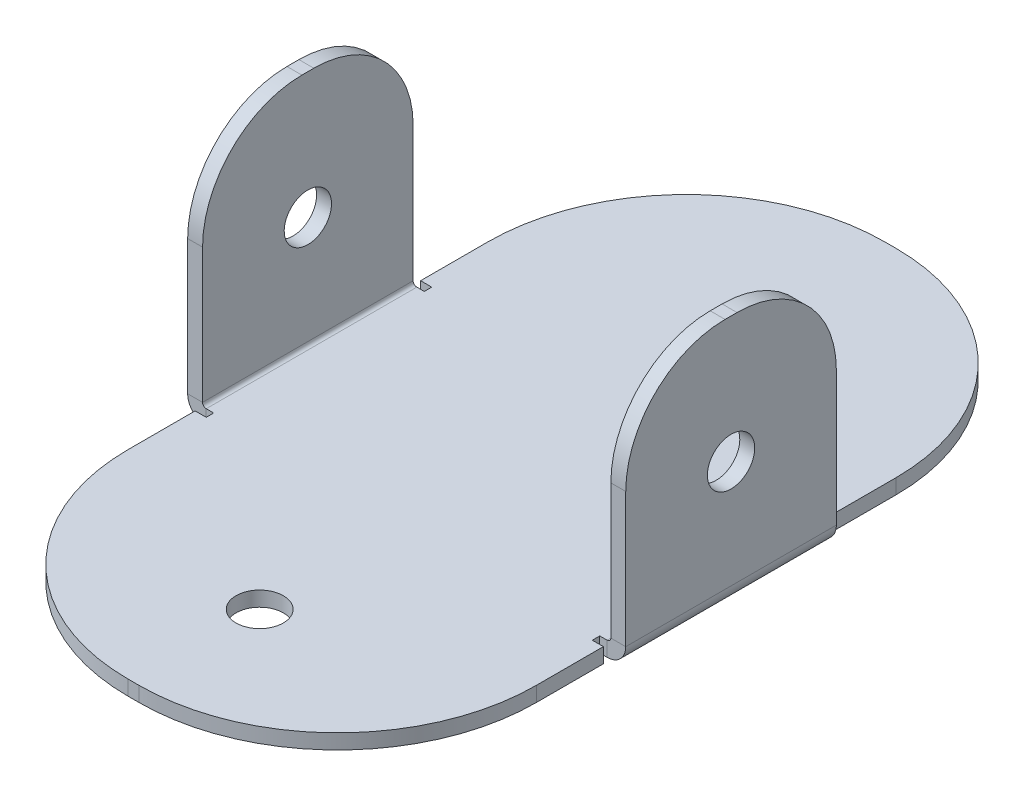
SolidWorks part; units mm, degrees
note: The reader was unsure of these and kept them because the rebuilt part matched: flange length of "Edge-Flange2", "Edge-Flange3".
ref_plane "Front Plane" through (0, 0, 0) normal (0, 0, 1) x (1, 0, 0)
ref_plane "Top Plane" through (0, 0, 0) normal (0, 1, 0) x (1, 0, 0)
ref_plane "Right Plane" through (0, 0, 0) normal (1, 0, 0) x (0, 0, -1)
sketch "Sketch1" plane through (0, 0, 0) normal (0, 1, 0) x (1, 0, 0)
  line L0 (0, -76.2) -> (0, -50.8) construction
  line L1 (-1.1, 76.2) -> (1.1, 76.2)
  line L2 (-41.1, 36.2) -> (-41.1, -36.2)
  line L3 (-1.1, -76.2) -> (1.1, -76.2)
  line L4 (41.1, 36.2) -> (41.1, -36.2)
  line L5 (-41.1, 76.2) -> (41.1, -76.2) construction
  line L6 (-41.1, -76.2) -> (41.1, 76.2) construction
  line L7 (0, 0) -> (5.4464, 0) construction
  arc A0 (1.1, 76.2) -> (41.1, 36.2) centre (1.1, 36.2) cw
  arc A1 (-1.1, 76.2) -> (-41.1, 36.2) centre (-1.1, 36.2) ccw
  arc A2 (1.1, -76.2) -> (41.1, -36.2) centre (1.1, -36.2) ccw
  arc A3 (-41.1, -36.2) -> (-1.1, -76.2) centre (-1.1, -36.2) ccw
  circle A4 centre (0, -50.8) radius 4.7625
  circle A5 centre (0, 50.8) radius 4.7625
  point P0 (0, 0)
  dimension "D1" = 40
base flange "Base-Flange1" sketch "Sketch1" thickness 3 reverse thickness direction no parameters "D1"=0.7366
edge flange "Edge-Flange2" sketch "Sketch14" flange angle 90 flange length 50.8 flange position material outside bend radius 0.7366 thickness 3 relief rectangular parameters "D6"=10
sketch "Sketch14" plane through (41.1, 0, 0) normal (1, 0, 0) x (0, 0, -1)
  line L0 (-36.2, 0) -> (36.2, 0) construction
  line L1 (-21.2, 0) -> (21.2, 0)
  line L2 (-21.2, 0) -> (-21.2, 27.8)
  line L3 (-1.2, 47.8) -> (1.2, 47.8)
  line L4 (21.2, 27.8) -> (21.2, 0)
  line L5 (36.2, -3) -> (36.2, 0) construction
  line L6 (0, 47.8) -> (0, 22.4) construction
  arc A0 (1.2, 47.8) -> (21.2, 27.8) centre (1.2, 27.8) cw
  arc A1 (-21.2, 27.8) -> (-1.2, 47.8) centre (-1.2, 27.8) cw
  circle A2 centre (0, 22.4) radius 4.7625
  dimension "D3" = 20
  dimension "D1" = 15
  dimension "D2" = 15
bend "EdgeBend3" bend radius 0.7366 bend angle 90 parameters "D5"=1
edge flange "Edge-Flange3" sketch "Sketch17" flange angle 90 flange length 50.8 flange position material outside bend radius 0.7366 thickness 3 relief rectangular parameters "D6"=10
sketch "Sketch17" plane through (-41.1, 0, 0) normal (-1, 0, 0) x (0, 0, 1)
  line L0 (-36.2, 0) -> (36.2, 0) construction
  line L1 (-21.2, 0) -> (21.2, 0)
  line L2 (-21.2, 0) -> (-21.2, 27.8)
  line L3 (-1.2, 47.8) -> (1.2, 47.8)
  line L4 (21.2, 27.8) -> (21.2, 0)
  line L5 (21.2, 27.8) -> (21.2, 0.7366) construction
  line L6 (36.2, -3) -> (36.2, 0) construction
  arc A0 (1.2, 47.8) -> (21.2, 27.8) centre (1.2, 27.8) cw
  arc A1 (-21.2, 27.8) -> (-1.2, 47.8) centre (-1.2, 27.8) cw
  circle A2 centre (0, 22.4) radius 4.7625 construction
  circle A3 centre (0, 22.4) radius 4.7625
  point P4 (-23.0554, 0)
  point P6 (21.2, 0.7366)
  dimension "D3" = 20
  dimension "D1" = 15
  dimension "D2" = 15
bend "EdgeBend4" bend radius 0.7366 bend angle 90 parameters "D5"=2
sketch "Bend-Lines1" [suppressed] plane through (0, 0, 0) normal (0, 1, 0) x (1, 0, 0)
sketch "Bounding-Box1" [suppressed] plane through (0, 0, 0) normal (0, 1, 0) x (1, 0, 0)
sheet metal parameters "Sheet-Metal1" thickness 3 parameters "D1"=0.7366
flat pattern "Flat-Pattern1" [suppressed]
sketch "Bend-Lines2" plane through (0, 0, 0) normal (0, 1, 0) x (1, 0, 0)
sketch3d "Bounding-Box2" [suppressed]
  line L0 (-42.2, -112.4, 0) -> (-42.2, 40, 0) construction
  line L1 (40, -112.4, 0) -> (40, 40, 0) construction
  line L2 (-42.2, -112.4, 0) -> (40, -112.4, 0) construction
  line L3 (-42.2, 40, 0) -> (40, 40, 0) construction
sheet metal parameters "Sheet-Metal3" thickness 3 parameters "D1"=0.7366
flat pattern "Flat-Pattern1"
sketch "Bend-Lines2" plane through (0, 0, 0) normal (0, 1, 0) x (1, 0, 0)
  line L0 (42.12, -21.2) -> (42.12, 21.2) construction
  line L1 (42.12, -21.2) -> (42.12, 21.2) construction
sketch3d "Bounding-Box2" [suppressed]
  line L0 (-94.3398, -26.029, 0) -> (12.6234, 65.2254, 0) construction
  line L1 (-5.7423, -129.878, 0) -> (101.2209, -38.6235, 0) construction
  line L2 (-94.3398, -26.029, 0) -> (-5.7423, -129.878, 0) construction
  line L3 (12.6234, 65.2254, 0) -> (101.2209, -38.6235, 0) construction
bend of the flat pattern "Flatten-<EdgeBend3>1"
sheet metal parameters "Sheet-Metal4" thickness 3 parameters "D1"=0.7366
flat pattern "Flat-Pattern1"
sketch "Bend-Lines2" plane through (0, 0, 0) normal (0, 1, 0) x (1, 0, 0)
  line L0 (42.12, -21.2) -> (42.12, 21.2) construction
  line L1 (42.12, -21.2) -> (42.12, 21.2) construction
  line L2 (-42.12, 21.2) -> (-42.12, -21.2) construction
  line L3 (-42.12, 21.2) -> (-42.12, -21.2) construction
sketch3d "Bounding-Box2" [suppressed]
  line L0 (-101.4608, -34.3011, 0) -> (9.4152, 63.6265, 0) construction
  line L1 (-11.6152, -136.0265, 0) -> (99.2608, -38.0989, 0) construction
  line L2 (-101.4608, -34.3011, 0) -> (-11.6152, -136.0265, 0) construction
  line L3 (9.4152, 63.6265, 0) -> (99.2608, -38.0989, 0) construction
bend of the flat pattern "Flatten-<EdgeBend3>1"
bend of the flat pattern "Flatten-<EdgeBend4>1"
